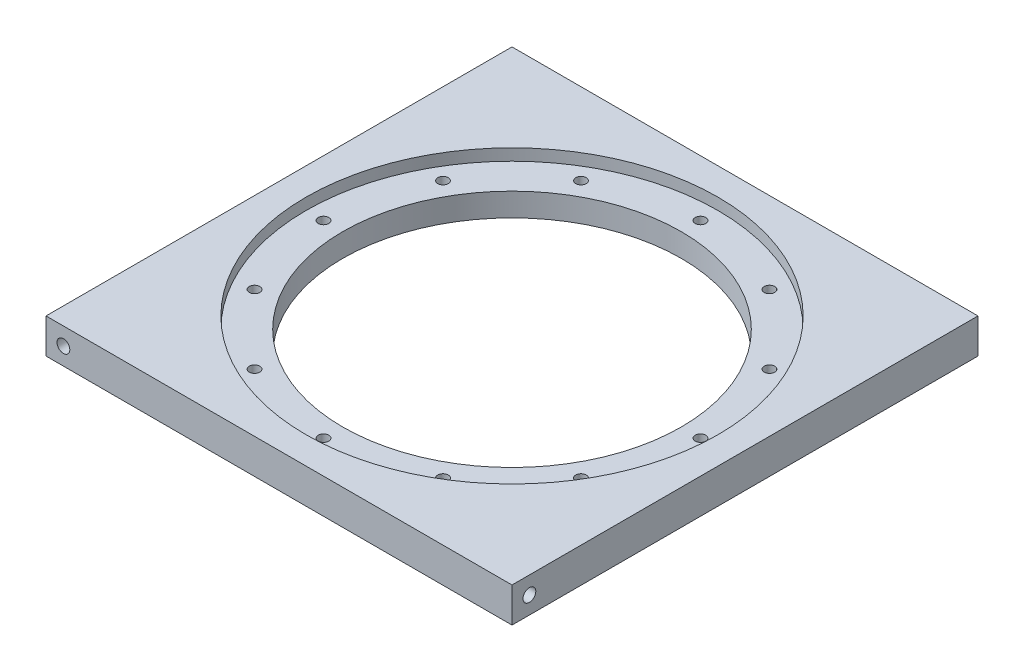
SolidWorks part; units mm, degrees
material "6061-T6 (SS)"
ref_plane "Front Plane" through (0, 0, 0) normal (0, 0, 1) x (1, 0, 0)
ref_plane "Top Plane" through (0, 0, 0) normal (0, 1, 0) x (1, 0, 0)
ref_plane "Right Plane" through (0, 0, 0) normal (1, 0, 0) x (0, 0, -1)
sketch "Sketch1" plane through (0, 0, 0) normal (0, 1, 0) x (1, 0, 0)
  line L5 (0, 0) -> (127.635, 0)
  line L6 (0, 0) -> (0, 127.635)
  line L7 (0, 127.635) -> (127.635, 127.635)
  line L8 (127.635, 0) -> (127.635, 127.635)
  dimension "D1" = 127.635
  dimension "D2" = 127.635
extrude "Boss-Extrude1" add sketch "Sketch1" along normal blind 9.525 contours L5 L8 L7 L6
sketch "Sketch5" plane through (0, 9.525, 0) normal (0, 1, 0) x (1, 0, 0)
  line L0 (63.8175, 0) -> (63.8175, 127.635) construction
  line L3 (0, 0) -> (127.635, 0) construction
  line L8 (0, 127.635) -> (127.635, 127.635) construction
  circle A0 centre (63.8175, 63.8175) radius 46.355
  dimension "D1" = 92.71
extrude "Cut-Extrude1" cut sketch "Sketch5" against normal blind 9.525 contours L0 A0 | A0 L0
sketch "Sketch6" plane through (127.635, 0, 0) normal (1, 0, 0) x (0, 0, -1)
  circle A0 centre (4.7625, 4.7625) radius 1.7526
  dimension "D1" = 3.5052
extrude "6-32 hole1" cut sketch "Sketch6" against normal blind 6.35
sketch "Sketch7" plane through (0, 0, -127.635) normal (0, 0, -1) x (-1, 0, 0)
  circle A0 centre (-122.8725, 4.7625) radius 1.7526
  dimension "D1" = 3.5052
sketch "Sketch8" plane through (0, 0, 0) normal (-1, 0, 0) x (0, 0, 1)
  circle A0 centre (-122.8725, 4.7625) radius 1.7526
  dimension "D1" = 3.5052
sketch "Sketch9" plane through (0, 0, 0) normal (0, 0, 1) x (1, 0, 0)
  circle A0 centre (4.7625, 4.7625) radius 1.7526
  dimension "D1" = 3.5052
extrude "6-32 hole2" cut sketch "Sketch7" against normal blind 6.35
extrude "6-32 hole3" cut sketch "Sketch8" against normal blind 6.35
extrude "6-32 hole4" cut sketch "Sketch9" against normal blind 6.35
sketch "Sketch11" plane through (0, 9.525, 0) normal (0, 1, 0) x (1, 0, 0)
  line L0 (63.8175, 63.8175) -> (63.8175, 115.443) construction
  circle A0 centre (63.8175, 115.443) radius 1.4351
  dimension "D2" = 2.8702
  dimension "D1" = 51.6255
extrude "Cut-Extrude3" cut sketch "Sketch11" against normal through all contours A0
pattern_circular "CirPattern1" count 12 over 360 about axis through (63.8175, 9.525, -63.8175) along (0, 1, 0) of "Cut-Extrude3"
sketch "Sketch12" plane through (0, 9.525, 0) normal (0, 1, 0) x (1, 0, 0)
  circle A0 centre (63.8175, 63.8175) radius 56.388
  dimension "D1" = 112.776
extrude "Cut-Extrude4" cut sketch "Sketch12" against normal blind 3.175
